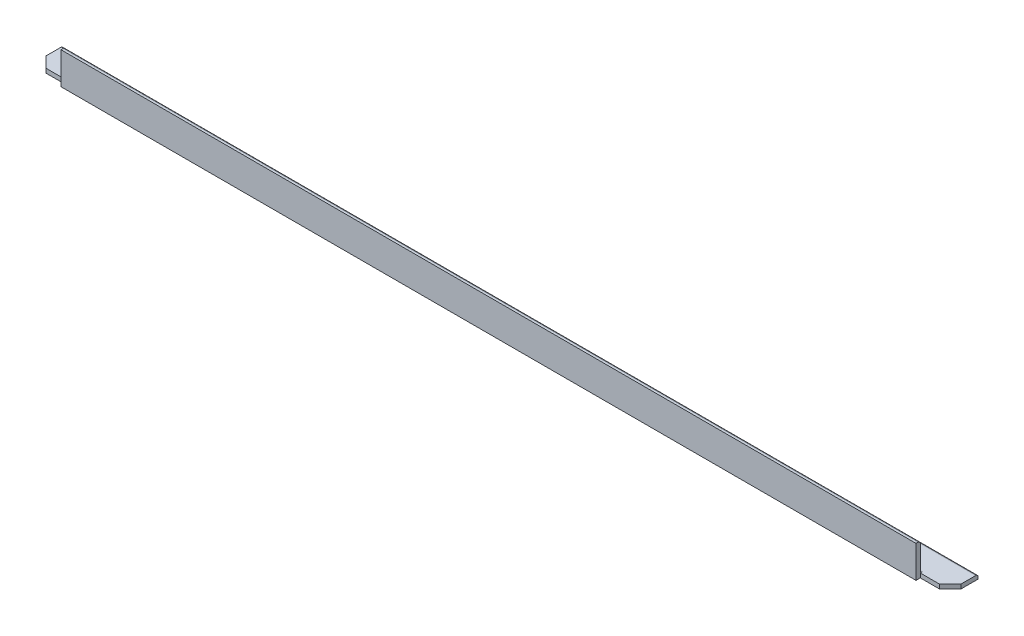
SolidWorks part; units mm, degrees
material "1060 Сплав"
ref_plane "Front" through (0, 0, 0) normal (0, 0, 1) x (1, 0, 0)
ref_plane "Top" through (0, 0, 0) normal (0, 1, 0) x (1, 0, 0)
ref_plane "Right" through (0, 0, 0) normal (1, 0, 0) x (0, 0, -1)
sketch "Эскиз1" plane through (0, 0, 0) normal (1, 0, 0) x (0, 0, -1)
  line L0 (0, 0) -> (0, 15)
  line L1 (0, 0) -> (15, 0)
  line L2 (0, 15) -> (1, 15)
  line L3 (2, 14) -> (2, 3)
  line L4 (3, 2) -> (14, 2)
  line L5 (15, 1) -> (15, 0)
  arc A0 (14, 2) -> (15, 1) centre (14, 1) cw
  arc A1 (1, 15) -> (2, 14) centre (1, 14) cw
  arc A2 (2, 3) -> (3, 2) centre (3, 3) ccw
  point P9 (15, 2)
  point P12 (2, 15)
  dimension "D5" = 1
  dimension "D1" = 15
  dimension "D2" = 15
  dimension "D3" = 2
  dimension "D4" = 2
extrude "Бобышка-Вытянуть1" add sketch "Эскиз1" along normal blind 428
sketch "Эскиз6" plane through (428, 0, 0) normal (1, 0, 0) x (0, 0, -1)
  line L0 (0, 0) -> (15, 0) construction
  line L1 (0, 15) -> (2, 15)
  line L2 (0, 15) -> (0, 0)
  line L3 (0, 0) -> (2, 0)
  line L4 (2, 0) -> (2, 2)
  line L5 (2, 2) -> (3, 2)
  line L6 (3, 2) -> (3, 15)
  line L7 (3, 15) -> (2, 15)
extrude "Вырез-Вытянуть5" cut sketch "Эскиз6" against normal blind 14
sketch "Эскиз7" plane through (0, 0, 0) normal (-1, 0, 0) x (0, 0, 1)
  line L0 (0, 0) -> (-15, 0) construction
  line L1 (0, 15) -> (-2, 15)
  line L2 (0, 15) -> (0, 0)
  line L3 (0, 0) -> (-2, 0)
  line L4 (-3, 2) -> (-2, 2)
  line L5 (-2, 2) -> (-2, 0)
  line L6 (-3, 2) -> (-3, 15)
  line L7 (-3, 15) -> (-2, 15)
extrude "Вырез-Вытянуть6" cut sketch "Эскиз7" against normal blind 14
sketch "Эскиз9" plane through (0, 2, 0) normal (0, 1, 0) x (1, 0, 0)
  line L0 (0, 2) -> (0, 7)
  line L1 (0, 14) -> (0, 2) construction
  line L2 (0, 7) -> (5, 2)
  line L3 (14, 2) -> (0, 2) construction
  line L4 (5, 2) -> (0, 2)
  line L5 (428, 2) -> (428, 7)
  line L6 (428, 14) -> (428, 2) construction
  line L7 (428, 7) -> (423, 2)
  line L8 (414, 2) -> (428, 2) construction
  line L9 (423, 2) -> (428, 2)
  dimension "D1" = 5
  dimension "D2" = 5
  dimension "D3" = 5
  dimension "D4" = 5
extrude "Вырез-Вытянуть7" cut sketch "Эскиз9" against normal through all
sketch "Эскиз10" plane through (0, 2, 0) normal (0, 1, 0) x (1, 0, 0)
  line L0 (428, 15) -> (0, 15) construction
  line L1 (0, 14) -> (0, 7) construction
  line L2 (428, 14) -> (428, 7) construction
  circle A0 centre (40, 8) radius 2.3
  circle A1 centre (388, 8) radius 2.3
  dimension "D1" = 4.6
  dimension "D2" = 7
  dimension "D3" = 40
  dimension "D4" = 4.6
  dimension "D5" = 7
  dimension "D6" = 40
extrude "Вырез-Вытянуть8" cut sketch "Эскиз10" against normal through all
chamfer "Фаска1" distance 2.05 angle 45 2 edges at (40, 2, -5.7) (388, 2, -5.7)
